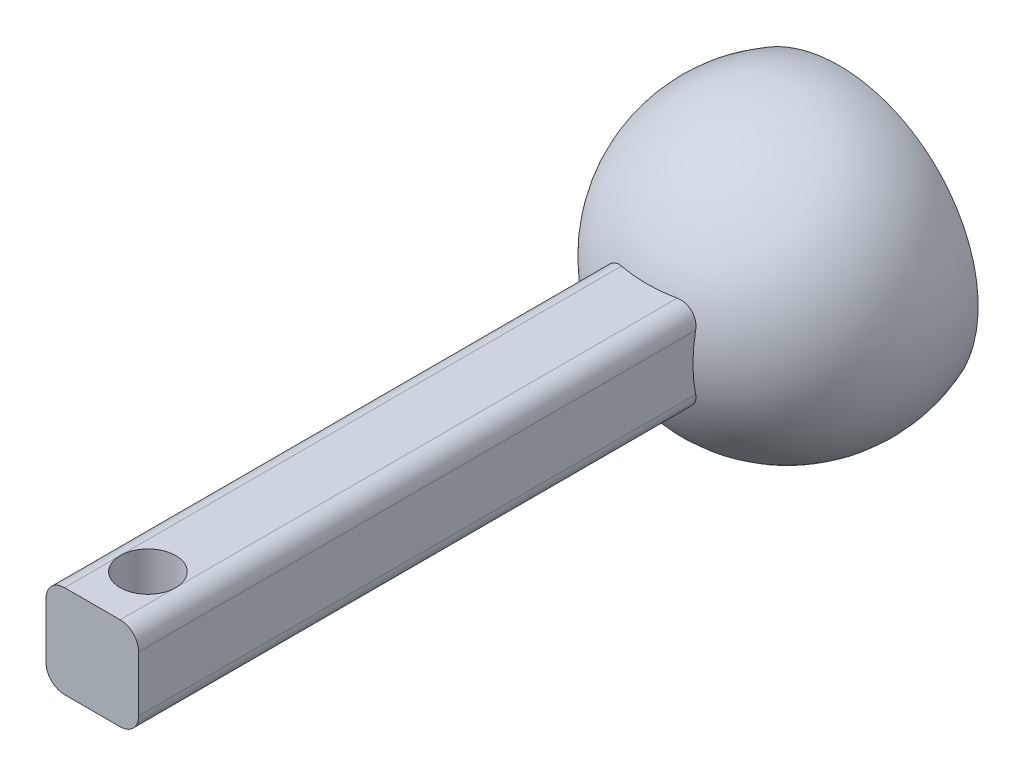
SolidWorks part; units mm, degrees
ref_plane "Front Plane" through (0, 0, 0) normal (0, 0, 1) x (1, 0, 0)
ref_plane "Top Plane" through (0, 0, 0) normal (0, 1, 0) x (1, 0, 0)
ref_plane "Right Plane" through (0, 0, 0) normal (1, 0, 0) x (0, 0, -1)
sketch "Sketch1" plane through (0, 0, 0) normal (0, 0, 1) x (1, 0, 0)
  line L0 (-0.5903, 15.2014) -> (-0.5903, -0.7986)
  arc A0 (-0.5903, 15.2014) -> (-0.5903, -0.7986) centre (-0.5903, 7.2014) cw
  dimension "D2" = 8
  dimension "D1" = 16
revolve "Revolve1" add sketch "Sketch1" angle 360 about L0
sketch "Sketch3" plane through (0, 0, 0) normal (0, 0, -1) x (-1, 0, 0)
  line L0 (0.5903, 15.2014) -> (0.5903, -0.7986) construction
  line L1 (8.5903, 7.2014) -> (-7.4097, 7.2014) construction
  line L3 (-1.9097, 9.7014) -> (3.0903, 9.7014)
  line L4 (-1.9097, 9.7014) -> (-1.9097, 4.7014)
  line L5 (-1.9097, 4.7014) -> (3.0903, 4.7014)
  line L6 (3.0903, 9.7014) -> (3.0903, 4.7014)
  line L7 (-1.9097, 9.7014) -> (3.0903, 4.7014) construction
  line L8 (-1.9097, 4.7014) -> (3.0903, 9.7014) construction
  circle A0 centre (0.5903, 7.2014) radius 8 construction
  point P6 (0.5903, 7.2014)
  dimension "D1" = 5
  dimension "D2" = 5
  dimension "D3" = 0
extrude "Boss-Extrude1" add sketch "Sketch3" against normal blind 37.5
sketch "Sketch4" plane through (0, 4.7014, 0) normal (0, -1, 0) x (1, 0, 0)
  line L0 (1.9097, 37.5) -> (-3.0903, 37.5) construction
  circle A0 centre (-0.5903, 34.5) radius 1.5
  point P5 (-0.5903, 37.5)
  dimension "D1" = 3
  dimension "D2" = 3
  dimension "D3" = 0
extrude "Cut-Extrude1" cut sketch "Sketch4" against normal blind 5
sketch "Sketch5" plane through (0, 0, 0) normal (0, 1, 0) x (1, 0, 0)
  line L1 (-1.7347, 13.2978) -> (1.7347, 13.2978)
  line L2 (-1.7347, 13.2978) -> (-1.7347, 12.1085)
  line L3 (-1.7347, 12.1085) -> (1.7347, 12.1085)
  line L4 (1.7347, 13.2978) -> (1.7347, 12.1085)
  line L5 (-1.7347, 13.2978) -> (1.7347, 12.1085) construction
  line L6 (-1.7347, 12.1085) -> (1.7347, 13.2978) construction
  point P0 (0, 12.7031)
extrude "Boss-Extrude2" add sketch "Sketch5" along normal blind 8 separate body
sketch "Sketch6" plane through (0, 0, -13.2978) normal (0, 0, -1) x (-1, 0, 0)
  line L1 (-9.9197, 15.2726) -> (10.1712, 15.2726)
  line L2 (-9.9197, 15.2726) -> (-9.9197, -1.1718)
  line L3 (-9.9197, -1.1718) -> (10.1712, -1.1718)
  line L4 (10.1712, 15.2726) -> (10.1712, -1.1718)
extrude "Cut-Extrude2" cut sketch "Sketch6" against normal blind 10.5
fillet "Fillet5" radius 1 1 edges at (-3.0903, 9.7014, 22.3382)
fillet "Fillet6" radius 1 1 edges at (1.9097, 9.7014, 22.3382)
fillet "Fillet7" radius 1 1 edges at (1.9097, 4.7014, 22.3382)
fillet "Fillet8" radius 1 1 edges at (-3.0903, 4.7014, 22.3382)
